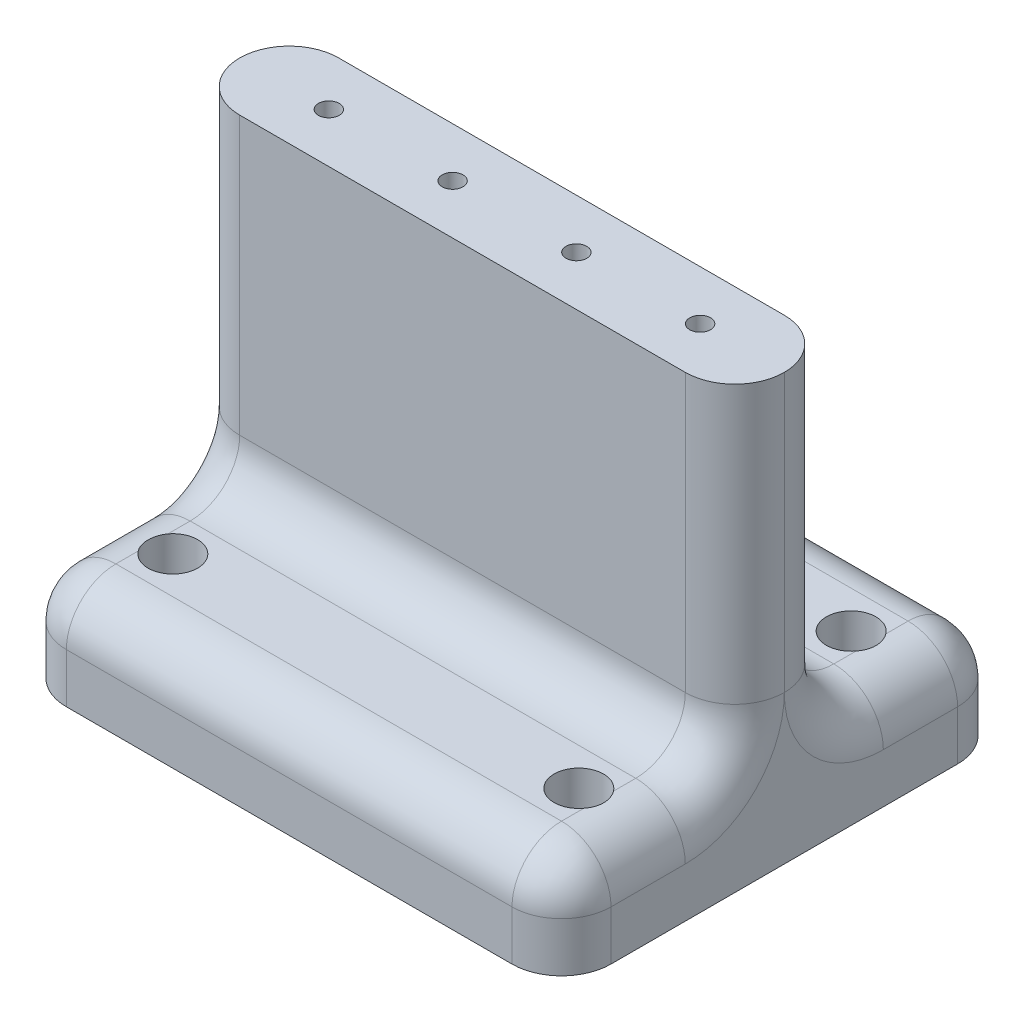
SolidWorks part; units mm, degrees
ref_plane "Front Plane" through (0, 0, 0) normal (0, 0, 1) x (1, 0, 0)
ref_plane "Top Plane" through (0, 0, 0) normal (0, 1, 0) x (1, 0, 0)
ref_plane "Right Plane" through (0, 0, 0) normal (1, 0, 0) x (0, 0, -1)
sketch "Sketch2" plane through (0, 0, 0) normal (0, 0, 1) x (1, 0, 0)
  line L1 (0, 0) -> (110, 0)
  line L2 (0, 0) -> (0, 86)
  line L3 (0, 86) -> (110, 86)
  line L4 (110, 0) -> (110, 86)
  dimension "D1" = 86
  dimension "D2" = 110
extrude "Boss-Extrude1" add sketch "Sketch2" along normal blind 20
sketch "Sketch3" plane through (110, 0, 0) normal (1, 0, 0) x (0, 0, -1)
  line L0 (-20, 0) -> (0, 20) construction
  line L1 (0, 0) -> (0, 86) construction
  line L2 (-20, 0) -> (0, 0) construction
  line L3 (0, 0) -> (-20, 20) construction
  line L4 (-20, 0) -> (-20, 86) construction
  line L6 (-55, 20) -> (35, 20)
  line L7 (-55, 20) -> (-55, 0)
  line L8 (-55, 0) -> (35, 0)
  line L9 (35, 20) -> (35, 0)
  line L10 (-55, 20) -> (35, 0) construction
  line L11 (-55, 0) -> (35, 20) construction
  point P12 (-10, 10)
  dimension "D1" = 45
  dimension "D2" = 90
extrude "Boss-Extrude2" add sketch "Sketch3" against normal up to surface (110 mm away) up to face at (0, 43, 10)
sketch "Sketch4" plane through (0, 20, 0) normal (0, 1, 0) x (1, 0, 0)
  line L0 (14, -55) -> (14, -20) construction
  line L1 (0, -55) -> (110, -55) construction
  line L2 (0, -20) -> (110, -20) construction
  line L3 (0, -55) -> (0, -20) construction
  line L4 (0, -10) -> (110, -10) construction
  line L5 (0, -20) -> (0, 0) construction
  line L6 (110, -20) -> (110, 0) construction
  line L7 (55, 35) -> (55, -55) construction
  line L8 (0, 35) -> (110, 35) construction
  circle A0 centre (14, -37.5) radius 1.9
  circle A1 centre (96, -37.5) radius 1.9
  circle A2 centre (96, 17.5) radius 1.9
  circle A3 centre (14, 17.5) radius 1.9
  point P8 (14, -37.5)
  point P21 (0, 0)
  dimension "D2" = 3.8
  dimension "D1" = 14
extrude "Cut-Extrude1" cut sketch "Sketch4" against normal blind 20
sketch "Sketch5" plane through (0, 20, 0) normal (0, 1, 0) x (1, 0, 0)
  line L0 (0, -10) -> (110, -10) construction
  line L1 (0, -20) -> (0, 0) construction
  line L2 (110, -20) -> (110, 0) construction
  line L3 (55, 35) -> (55, -55) construction
  line L4 (0, 35) -> (110, 35) construction
  line L5 (0, -55) -> (110, -55) construction
  circle A0 centre (96, -37.5) radius 5
  circle A1 centre (14, -37.5) radius 5
  circle A2 centre (14, 17.5) radius 5
  circle A3 centre (96, 17.5) radius 5
  dimension "D1" = 10
extrude "Cut-Extrude2" cut sketch "Sketch5" against normal offset from surface (10 mm away) 10 up to face at (14, 0, -19.4)
fillet "Fillet1" radius 10 16 edges at (0, 53, 0) (110, 53, 0) (0, 53, 20) (110, 53, 20) (55, 20, 0) (55, 20, 20) (0, 10, -35) (0, 10, 55) (110, 10, 55) (110, 10, -35) (0, 20, -17.5) (55, 20, -35) (110, 20, -17.5) (0, 20, 37.5) (110, 20, 37.5) (55, 20, 55)
sketch "Sketch6" plane through (0, 86, 0) normal (0, 1, 0) x (1, 0, 0)
  line L0 (0, -10) -> (110, -10) construction
  circle A3 centre (18, -10) radius 2.1
  circle A4 centre (43, -10) radius 2.1
  circle A5 centre (68, -10) radius 2.1
  circle A6 centre (93, -10) radius 2.1
  dimension "D1" = 18
  dimension "D2" = 4.2
  dimension "D4" = 25
  dimension "D3" = 4
extrude "Cut-Extrude3" cut sketch "Sketch6" against normal blind 10
